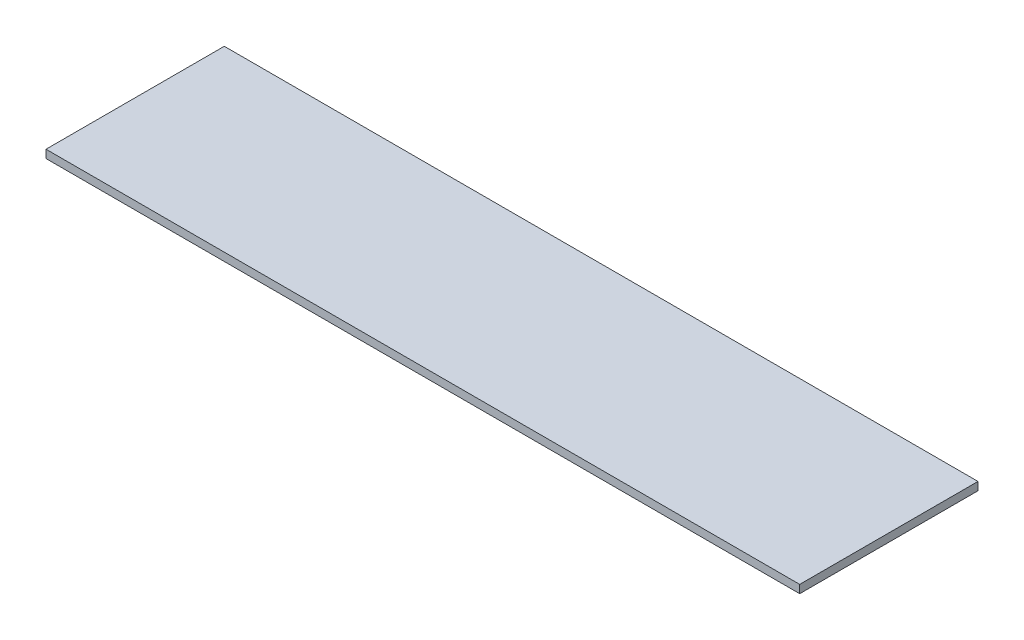
SolidWorks part; units mm, degrees
ref_plane "Front Plane" through (0, 0, 0) normal (0, 0, 1) x (1, 0, 0)
ref_plane "Top Plane" through (0, 0, 0) normal (0, 1, 0) x (1, 0, 0)
ref_plane "Right Plane" through (0, 0, 0) normal (1, 0, 0) x (0, 0, -1)
sketch "Sketch1" plane through (0, 0, 0) normal (0, 1, 0) x (1, 0, 0)
  line L1 (-232.5, 55) -> (232.5, 55)
  line L2 (-232.5, 55) -> (-232.5, -55)
  line L3 (-232.5, -55) -> (232.5, -55)
  line L4 (232.5, 55) -> (232.5, -55)
  line L5 (-232.5, 55) -> (232.5, -55) construction
  line L6 (-232.5, -55) -> (232.5, 55) construction
  point P0 (0, 0)
  dimension "D1" = 465
  dimension "D2" = 110
extrude "Boss-Extrude1" add sketch "Sketch1" along normal blind 5
